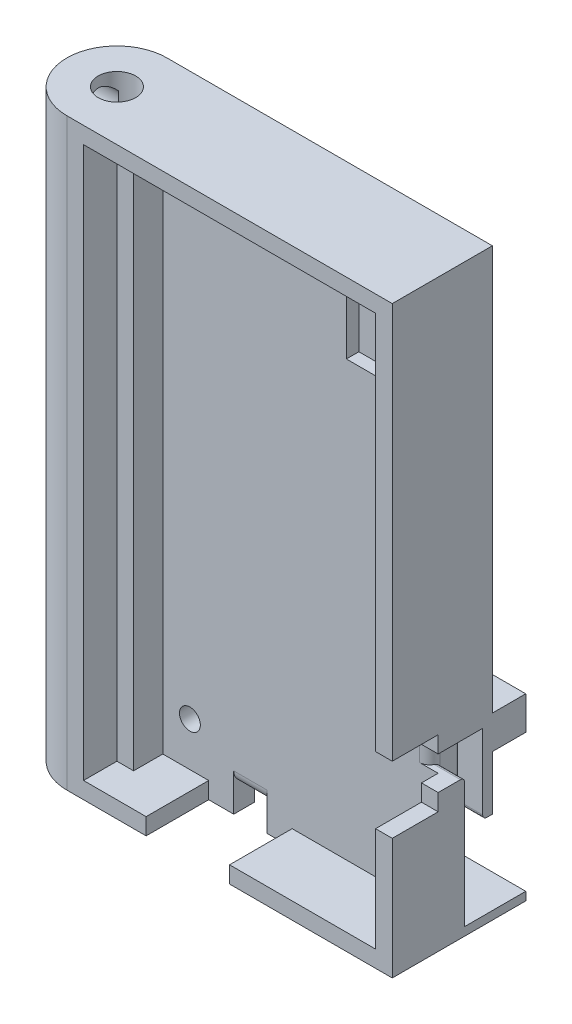
SolidWorks part; units mm, degrees
ref_plane "Front Plane" through (0, 0, 0) normal (0, 0, 1) x (1, 0, 0)
ref_plane "Top Plane" through (0, 0, 0) normal (0, 1, 0) x (1, 0, 0)
ref_plane "Right Plane" through (0, 0, 0) normal (1, 0, 0) x (0, 0, -1)
sketch "Sketch1" plane through (0, 0, 0) normal (0, 0, 1) x (1, 0, 0)
  line L1 (0, 0) -> (39, 0)
  line L2 (0, 0) -> (0, 70)
  line L3 (0, 70) -> (39, 70)
  line L4 (39, 0) -> (39, 70)
  dimension "D1" = 70
  dimension "D2" = 39
extrude "Base" add sketch "Sketch1" along normal blind 4.5
sketch "Sketch2" plane through (0, 0, 4.5) normal (0, 0, 1) x (1, 0, 0)
  line L0 (0, 70) -> (0, 0) construction
  line L1 (39, 70) -> (0, 70)
  line L2 (39, 70) -> (39, 66)
  line L3 (39, 66) -> (0, 66)
  line L4 (0, 70) -> (0, 66)
  line L5 (0, 0) -> (39, 0) construction
  line L6 (0, 66) -> (4, 66)
  line L7 (0, 66) -> (0, 0)
  line L8 (0, 0) -> (4, 0)
  line L9 (4, 66) -> (4, 0)
  line L10 (39, 0) -> (39, 70) construction
  line L11 (4, 0) -> (39, 0)
  line L12 (4, 0) -> (4, 4)
  line L13 (4, 4) -> (39, 4)
  line L14 (39, 0) -> (39, 4)
  line L16 (39, 66) -> (35, 66)
  line L17 (39, 66) -> (39, 4)
  line L18 (39, 4) -> (35, 4)
  line L19 (35, 66) -> (35, 4)
  line M6 (0, 70) -> (0, 0)
  line M7 (0, 0) -> (39, 0)
  line M8 (39, 0) -> (39, 70)
  line M9 (39, 70) -> (0, 70)
  dimension "D1" = 4
  dimension "D2" = 4
  dimension "D3" = 4
  dimension "D4" = 4
extrude "Walls" add sketch "Sketch2" along normal blind 7.5 contours L3 M8 M9 M6 | L3 L19 L13 M8 | L9 L3 M6 M7 | L13 L9 M7 M8 region at (19.5, 68, 4.5) region at (37, 35, 4.5) region at (2, 33, 4.5) region at (21.5, 2, 4.5)
sketch "Sketch3" plane through (0, 4, 0) normal (0, 1, 0) x (1, 0, 0)
  line L0 (4, -4.5) -> (35, -4.5) construction
  line L1 (9.5, -4.5) -> (19.5, -4.5)
  line L2 (9.5, -4.5) -> (9.5, -12)
  line L3 (9.5, -12) -> (19.5, -12)
  line L4 (19.5, -4.5) -> (19.5, -12)
  line L5 (4, -12) -> (35, -12) construction
  line L6 (4, -12) -> (4, -4.5) construction
  dimension "D1" = 5.5
  dimension "D2" = 15.5
extrude "PWR connector hole" cut sketch "Sketch3" against normal blind 4
sketch "Sketch4" plane through (35, 0, 0) normal (-1, 0, 0) x (0, 0, 1)
  line L0 (4.5, 66) -> (4.5, 4) construction
  line L1 (4.5, 14.5) -> (12, 14.5)
  line L2 (4.5, 14.5) -> (4.5, 22.5)
  line L3 (4.5, 22.5) -> (12, 22.5)
  line L4 (12, 14.5) -> (12, 22.5)
  line L5 (12, 66) -> (12, 4) construction
  line L6 (12, 4) -> (4.5, 4) construction
  dimension "D1" = 10.5
  dimension "D2" = 18.5
extrude "GPS connector hole" cut sketch "Sketch4" against normal blind 4
sketch "Sketch5" plane through (0, 0, 4.5) normal (0, 0, 1) x (1, 0, 0)
  line L0 (4, 4) -> (9.5, 4) construction
  line L1 (4, 66) -> (4, 4) construction
  line L2 (19.5, 66) -> (19.5, 4) construction
  line L3 (35, 66) -> (4, 66) construction
  line L5 (19.5, 35) -> (4, 35) construction
  line L6 (4, 66) -> (4, 4) construction
  circle A0 centre (7.25, 7.25) radius 1.25
  circle A1 centre (31.75, 7.25) radius 1.25
  circle A2 centre (7.25, 62.75) radius 1.25
  dimension "D1" = 3.25
  dimension "D3" = 2.5
  dimension "D2" = 3.25
extrude "Mounting holes" cut sketch "Sketch5" against normal blind 4
sketch "Sketch7" plane through (0, 0, 0) normal (0, 0, -1) x (-1, 0, 0)
  line L0 (-39, 0) -> (-39, 18.5) construction
  line L1 (-39, 0) -> (-39, 70) construction
  line L3 (-39, 1) -> (-8, 1)
  line L4 (-39, 1) -> (-39, 17.5)
  line L5 (-39, 17.5) -> (-8, 17.5)
  line L6 (-8, 1) -> (-8, 17.5)
  line L9 (0, 0) -> (-39, 0) construction
  line L10 (-39, 0) -> (-7, 0)
  line L11 (-7, 0) -> (-7, 18.5)
  line L12 (-7, 18.5) -> (-39, 18.5)
  line L13 (-39, 18.5) -> (-39, 17.5)
  line L14 (-39, 1) -> (-39, 0)
  line M8 (-39, 70) -> (-39, 0)
  line M9 (-39, 0) -> (0, 0)
  dimension "D1" = 18.5
  dimension "D2" = 1
  dimension "D3" = 16.5
  dimension "D4" = 31
  dimension "D5" = 32
  dimension "D6" = 18.5
extrude "GPS mount" add sketch "Sketch7" along normal blind 4 contours L11 L12 L5 L6 L3 M8 M9 region at (23.5, 0.6304, 0)
sketch "Sketch11" plane through (0, 0, 0) normal (0, 0, -1) x (-1, 0, 0)
  line L0 (0, 0) -> (-7, 0) construction
  line L1 (-4, 0) -> (-5, 0)
  line L2 (-4, 0) -> (-4, 21.5)
  line L3 (-4, 21.5) -> (-5, 21.5)
  line L4 (-5, 0) -> (-5, 21.5)
  line L5 (-7, 0) -> (-7, 18.5) construction
  line L7 (0, 70) -> (0, 0) construction
  line L8 (-5, 21.5) -> (-22, 21.5)
  line L9 (-5, 21.5) -> (-5, 20.5)
  line L10 (-5, 20.5) -> (-22, 20.5)
  line L11 (-22, 21.5) -> (-22, 20.5)
  line L12 (-7, 18.5) -> (-39, 18.5) construction
  line L13 (-39, 18.5) -> (-27, 18.5)
  line L14 (-39, 18.5) -> (-39, 21.5)
  line L15 (-39, 21.5) -> (-27, 21.5)
  line L16 (-27, 18.5) -> (-27, 21.5)
  line M5 (-7, 0) -> (0, 0)
  line M9 (-39, 18.5) -> (-7, 18.5)
  dimension "D1" = 1
  dimension "D2" = 2
  dimension "D3" = 21.5
  dimension "D4" = 1
  dimension "D5" = 22
  dimension "D6" = 5
  dimension "D7" = 12
  dimension "D8" = 3
extrude "PWR cable holder1" add sketch "Sketch11" along normal blind 4 contours L4 L2 L3 M5 | L8 L11 L10 L4 | L16 L15 L14 M9 region at (4.5, 10.75, 0) region at (13.5, 21, 0) region at (33, 20, 0)
sketch "Sketch12" plane through (0, 0, 0) normal (0, -1, 0) x (1, 0, 0)
  line L0 (19.5, 4.5) -> (9.5, 4.5) construction
  line L1 (5, 0) -> (16.5, 0)
  line L2 (5, 0) -> (5, 2)
  line L3 (5, 2) -> (16.5, 2)
  line L4 (16.5, 0) -> (16.5, 2)
  line L5 (9.5, 4.5) -> (9.5, 12) construction
  line L6 (12.5, 4.5) -> (16.5, 4.5)
  line L7 (12.5, 4.5) -> (12.5, 2)
  line L8 (12.5, 2) -> (16.5, 2)
  line L9 (16.5, 4.5) -> (16.5, 2)
  line L10 (19.5, 12) -> (19.5, 4.5) construction
  line M5 (19.5, 4.5) -> (9.5, 4.5)
  line M13 (5, 0) -> (7, 0)
  dimension "D1" = 2
  dimension "D2" = 3
  dimension "D3" = 3
  dimension "D4" = 0
extrude "PWR cable holder2" cut sketch "Sketch12" against normal blind 3 contours L1 L4 L3 L2 M13 | L9 L7 L3 M5 region at (10.75, 0, 1) region at (14.5, 0, 3.25)
fillet "PWR fillet" radius 1.5 2 edges at (14.5, 3, 4.5) (6, 3, 0)
fillet "PWR fillet2" radius 1 1 edges at (27, 21.5, -2)
fillet "PWR fillet3" radius 0.5 2 edges at (22, 21.5, -2) (22, 20.5, -2)
sketch "Sketch13" plane through (39, 0, 0) normal (1, 0, 0) x (0, 0, -1)
  line L0 (-4.5, 22.5) -> (-4.5, 14.5) construction
  line L1 (-4.5, 20.5) -> (-2.3266, 20.5)
  line L2 (-4.5, 20.5) -> (-4.5, 16.5)
  line L3 (-4.5, 16.5) -> (-2.3266, 16.5)
  line L4 (-2.3266, 20.5) -> (-2.3266, 16.5)
  line L5 (-12, 22.5) -> (-4.5, 22.5) construction
  line L6 (-4.5, 14.5) -> (-12, 14.5) construction
  line L7 (-2.3266, 16.5) -> (-2.3266, 11)
  line L8 (0, 1) -> (-2.3266, 1)
  line L9 (0, 1) -> (0, 11)
  line L10 (0, 11) -> (-2.3266, 11)
  line L11 (-2.3266, 1) -> (-2.3266, 11)
  line L17 (-2.3266, 16.5) -> (-3.3266, 16.5)
  line L18 (-2.3266, 11) -> (-1.1566, 11)
  line L19 (-2.3266, 11) -> (-2.3266, 20.5)
  line L20 (-2.3266, 20.5) -> (-1.1566, 20.5)
  line L21 (-1.1566, 11) -> (-1.1566, 20.5)
  line L22 (-2.3266, 16.5) -> (-2.3266, 1)
  line L23 (-2.3266, 1) -> (-3.3266, 1)
  line L24 (-3.3266, 16.5) -> (-3.3266, 1)
  line M19 (-4.5, 22.5) -> (-4.5, 14.5)
  line M27 (0, 1) -> (0, 17.5)
  dimension "D1" = 2
  dimension "D2" = 2
  dimension "D3" = 10
  dimension "D4" = 1.17
  dimension "D5" = 2.3266
  dimension "D6" = 1
extrude "GPS cable holder" cut sketch "Sketch13" against normal blind 3 contours L11 L8 L10 M27 | L3 L24 L23 L11 L7 | L10 L21 L20 L4 L7 | L4 L1 L3 M19 region at (39, 18.5, 3.4133) region at (39, 15.75, 1.7416) region at (39, 8.75, 2.8266) region at (39, 6, 1.1633)
fillet "GPS fillet" radius 1.25 2 edges at (36, 6, 0) (36, 18.5, 4.5)
fillet "GPS fillet 2" radius 0.5 2 edges at (37.4988, 16.5, 3.3266) (37.4983, 11, 1.1566)
sketch "Sketch15" plane through (0, 0, 0) normal (0, -1, 0) x (1, 0, 0)
  line L0 (0, 12) -> (0, 0) construction
  circle A0 centre (0, 6) radius 6
extrude "Ballon mount" add sketch "Sketch15" against normal blind 70
sketch "Sketch16" plane through (0, 0, 0) normal (0, -1, 0) x (1, 0, 0)
  line L0 (0, 0) -> (0, 6) construction
  circle A0 centre (0, 6) radius 2.25
  dimension "D1" = 4.5
extrude "Balloon mount hole" cut sketch "Sketch16" against normal blind 70
ref_plane "Plane1" through (-6, 0, 0) normal (-1, 0, 0) x (0, 0, 1)
sketch "Sketch21" plane through (-6, 0, 0) normal (-1, 0, 0) x (0, 0, 1)
  line L0 (6, 0) -> (6, 3.5) construction
  line L1 (0, 0) -> (12, 0) construction
  line L2 (0, 35) -> (12, 35) construction
  line L3 (0, 70) -> (0, 0) construction
  line L4 (12, 70) -> (12, 0) construction
  circle A0 centre (6, 3.5) radius 2.25
  circle A1 centre (6, 66.5) radius 2.25
  dimension "D2" = 4.5
  dimension "D1" = 3.5
extrude "Safety mount" cut sketch "Sketch21" against normal blind 4.5
sketch "Sketch22" plane through (0, 0, 12) normal (0, 0, 1) x (1, 0, 0)
  line L0 (19.5, 0) -> (39, 0) construction
  line L1 (2, 68) -> (37, 68)
  line L2 (2, 68) -> (2, 2)
  line L3 (2, 2) -> (37, 2)
  line L4 (37, 68) -> (37, 2)
  line L5 (39, 0) -> (39, 14.5) construction
  line L8 (39, 70) -> (0, 70) construction
  dimension "D1" = 35
  dimension "D2" = 2
  dimension "D3" = 2
  dimension "D4" = 2
extrude "Lid hole" cut sketch "Sketch22" against normal blind 7.5
sketch "Sketch25" plane through (2, 0, 0) normal (1, 0, 0) x (0, 0, -1)
  line L0 (-7.0308, 68) -> (-12, 68) construction
  line L1 (-4.5, 2) -> (-8, 2)
  line L2 (-4.5, 2) -> (-4.5, 68)
  line L3 (-4.5, 68) -> (-8, 68)
  line L4 (-8, 2) -> (-8, 68)
  dimension "D1" = 3.5
extrude "Correction" add sketch "Sketch25" along normal blind 2
sketch "Sketch28" plane through (0, 0, 4.5) normal (0, 0, 1) x (1, 0, 0)
  line L0 (34.75, 18.5) -> (39, 18.5) construction
  line L1 (37, 22.5) -> (39, 22.5)
  line L2 (37, 22.5) -> (37, 20.5)
  line L3 (37, 20.5) -> (39, 20.5)
  line L4 (39, 22.5) -> (39, 20.5)
  line L5 (34.75, 16.5) -> (34.75, 20.5) construction
  line L6 (37, 14.5) -> (39, 14.5)
  line L7 (39, 14.5) -> (39, 16.5)
  line L8 (37, 16.5) -> (39, 16.5)
  line L9 (37, 14.5) -> (37, 16.5)
extrude "Smaller walls" add sketch "Sketch28" along normal blind 2
sketch "Sketch29" plane through (0, 0, 4.5) normal (0, 0, 1) x (1, 0, 0)
  line L2 (37, 68) -> (26, 68)
  line L4 (37, 68) -> (37, 54)
  line L5 (37, 54) -> (26, 54)
  line L6 (26, 68) -> (26, 54)
  dimension "D1" = 11
  dimension "D2" = 14
extrude "Antenna space" cut sketch "Sketch29" against normal blind 1.5
